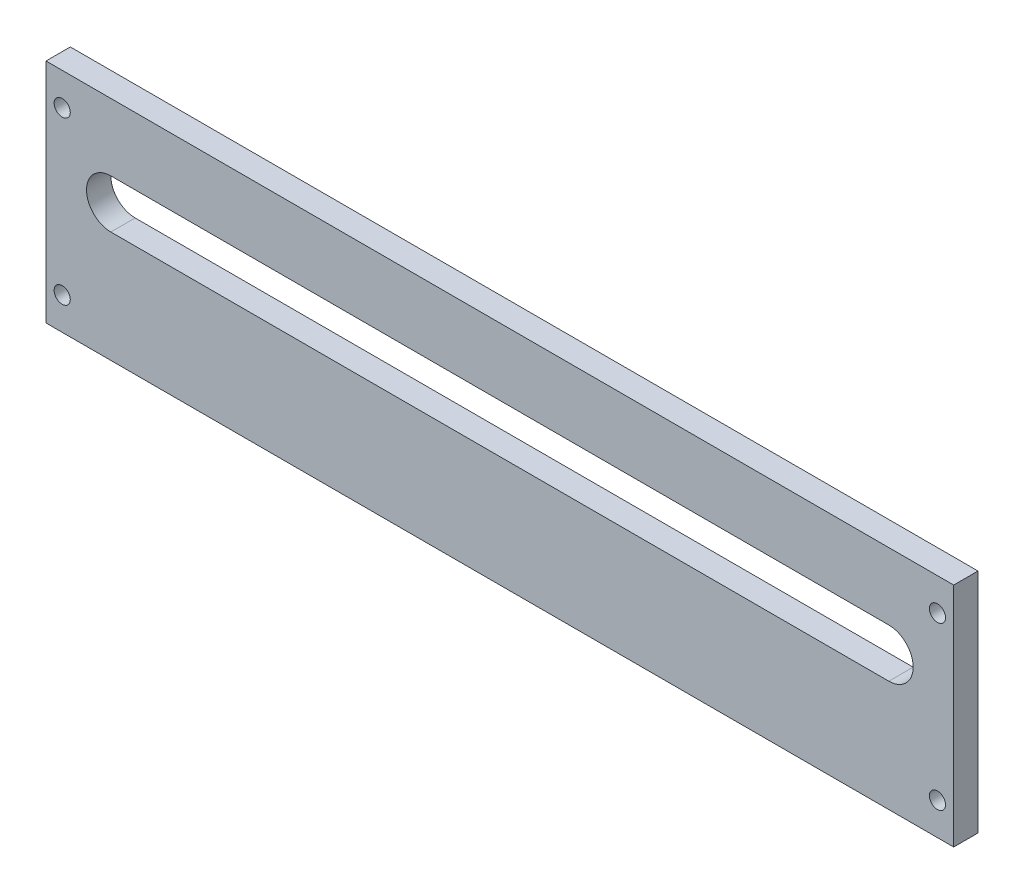
SolidWorks part; units mm, degrees
ref_plane "Front Plane" through (0, 0, 0) normal (0, 0, 1) x (1, 0, 0)
ref_plane "Top Plane" through (0, 0, 0) normal (0, 1, 0) x (1, 0, 0)
ref_plane "Right Plane" through (0, 0, 0) normal (1, 0, 0) x (0, 0, -1)
sketch "Sketch1" plane through (0, 0, 0) normal (0, 0, 1) x (1, 0, 0)
  line L1 (0, 0) -> (355.6, 0)
  line L2 (0, 0) -> (0, 88.9)
  line L3 (0, 88.9) -> (355.6, 88.9)
  line L4 (355.6, 0) -> (355.6, 88.9)
  dimension "D1" = 88.9
  dimension "D2" = 355.6
extrude "Boss-Extrude1" add sketch "Sketch1" along normal blind 9.525
sketch "Sketch2" plane through (0, 0, 9.525) normal (0, 0, 1) x (1, 0, 0)
  line L0 (0, 88.9) -> (0, 0) construction
  line L1 (355.6, 88.9) -> (0, 88.9) construction
  line L2 (0, 0) -> (355.6, 0) construction
  line L3 (355.6, 0) -> (355.6, 88.9) construction
  circle A0 centre (6.35, 76.2) radius 3.1623
  circle A1 centre (6.35, 12.7) radius 3.1623
  circle A2 centre (349.25, 76.2) radius 3.1623
  circle A3 centre (349.25, 12.7) radius 3.1623
  dimension "D1" = 6.3246
  dimension "D2" = 6.3246
  dimension "D3" = 6.3246
  dimension "D4" = 6.3246
  dimension "D5" = 6.35
  dimension "D6" = 12.7
  dimension "D7" = 6.35
  dimension "D8" = 12.7
  dimension "D9" = 12.7
  dimension "D10" = 12.7
  dimension "D11" = 6.35
  dimension "D12" = 6.35
extrude "Cut-Extrude1" cut sketch "Sketch2" against normal through all
sketch "Sketch3" plane through (0, 0, 9.525) normal (0, 0, 1) x (1, 0, 0)
  line L0 (25.4, 53.1) -> (330.2, 53.1) construction
  line L1 (25.4, 62.625) -> (330.2, 62.625)
  line L2 (25.4, 43.575) -> (330.2, 43.575)
  line L3 (0, 88.9) -> (0, 0) construction
  line L5 (355.6, 88.9) -> (0, 88.9) construction
  arc A0 (25.4, 62.625) -> (25.4, 43.575) centre (25.4, 53.1) ccw
  arc A1 (330.2, 43.575) -> (330.2, 62.625) centre (330.2, 53.1) ccw
  point P2 (177.8, 53.1)
  dimension "D1" = 9.525
  dimension "D2" = 304.8
  dimension "D3" = 25.4
  dimension "D4" = 35.8
extrude "Cut-Extrude2" cut sketch "Sketch3" against normal through all
